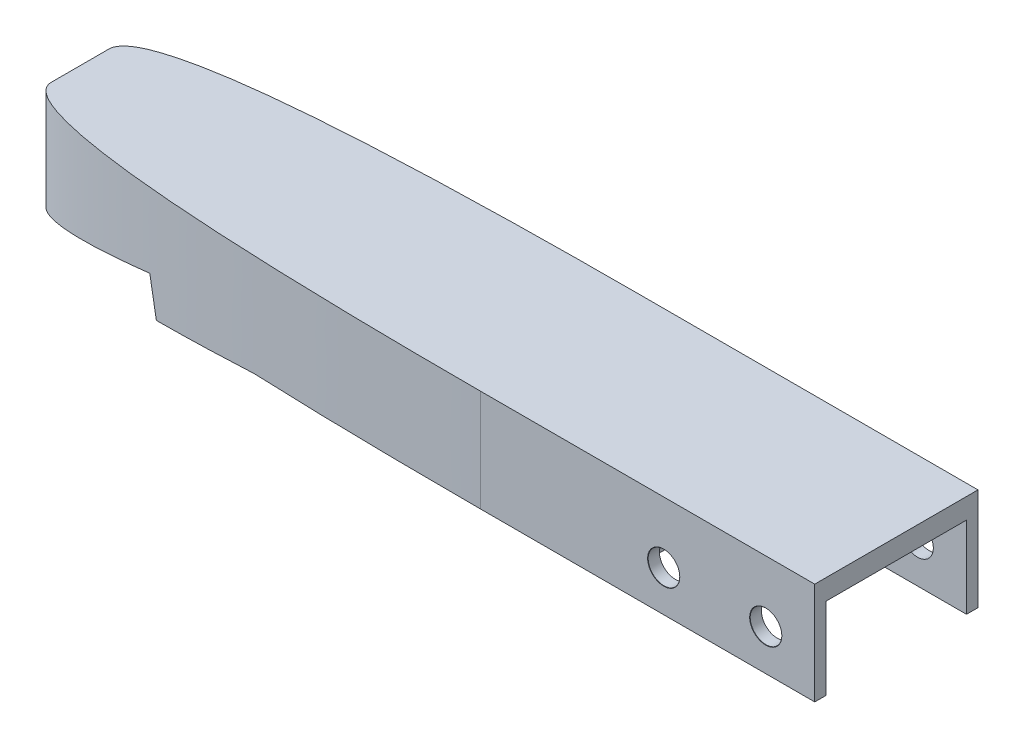
SolidWorks part; units mm, degrees
ref_plane "Front Plane" through (0, 0, 0) normal (0, 0, 1) x (1, 0, 0)
ref_plane "Top Plane" through (0, 0, 0) normal (0, 1, 0) x (1, 0, 0)
ref_plane "Right Plane" through (0, 0, 0) normal (1, 0, 0) x (0, 0, -1)
sketch "Sketch1" plane through (0, 0, 0) normal (0, 1, 0) x (1, 0, 0)
  line L1 (-40, 8) -> (40, 8)
  line L2 (-40, 8) -> (-40, -8)
  line L3 (-40, -8) -> (40, -8)
  line L4 (40, 8) -> (40, -8)
  line L5 (-40, 8) -> (40, -8) construction
  line L6 (-40, -8) -> (40, 8) construction
  point P0 (0, 0)
  dimension "D1" = 16
  dimension "D2" = 80
extrude "Boss-Extrude1" add sketch "Sketch1" along normal blind 10
sketch "Sketch3" plane through (0, 0, 0) normal (0, 1, 0) x (1, 0, 0)
  line L0 (40, -8) -> (40, 8) construction
  line L1 (40, -6.873) -> (19.746, -6.873)
  line L2 (40, -6.873) -> (40, 6.873)
  line L3 (40, 6.873) -> (19.746, 6.873)
  line L4 (19.746, -6.873) -> (19.746, 6.873)
  point P6 (19.746, 0)
  point P12 (40, 0)
  dimension "D1" = 13.746
  dimension "D2" = 20.254
extrude "Cut-Extrude1" cut sketch "Sketch3" along normal blind 8
sketch "Sketch4" plane through (0, 0, 8) normal (0, 0, 1) x (1, 0, 0)
  line L0 (25.2, 4) -> (35.2, 4) construction
  line L4 (19.746, 0) -> (40, 0)
  line L5 (19.746, 8) -> (19.746, 0)
  line L6 (40, 8) -> (19.746, 8)
  line L7 (40, 0) -> (40, 8)
  line L9 (19.746, 8) -> (19.746, 0) construction
  line L10 (40, 8) -> (19.746, 8) construction
  line L11 (40, 0) -> (40, 8) construction
  line L13 (19.746, 0) -> (40, 0)
  circle A0 centre (35.2, 4) radius 1.377
  circle A1 centre (25.2, 4) radius 1.377
  point P6 (30.2, 4)
  point P10 (19.746, 4)
  dimension "D2" = 2.754
  dimension "D3" = 10
  dimension "D4" = 4.8
  dimension "D1" = 0
sketch "Sketch6" plane through (0, 0, 8) normal (0, 0, 1) x (1, 0, 0)
  line L0 (-40, 10) -> (-40, 0) construction
  line L1 (-40, 0) -> (-26.2624, 2.6977)
  line L2 (-40, 0) -> (-40, -17.9177)
  line L3 (-40, -17.9177) -> (-22.2141, -17.9177)
  line L4 (-26.2624, 2.6977) -> (-22.2141, -17.9177)
  dimension "D1" = 101.11
  dimension "D2" = 14
  dimension "D3" = 90
extrude "Cut-Extrude3" cut sketch "Sketch6" against normal through all
sketch "Sketch9" plane through (0, 0, 8) normal (0, 0, 1) x (1, 0, 0)
  line L1 (-25.7326, 0) -> (-25.5531, -0.9142)
  line L7 (-25.5531, -0.9142) -> (-15.3096, 0)
  line L8 (-25.7326, 0) -> (40, 0) construction
  line L9 (-15.3096, 0) -> (-25.7326, 0)
  line L10 (-26.2624, 2.6977) -> (-25.7326, 0) construction
  dimension "D1" = 96.01
extrude "Boss-Extrude3" add sketch "Sketch9" against normal up to surface (16 mm away) up to face at (-8.6658, 3.783, -8)
sketch "Sketch7" plane through (0, 10, 0) normal (0, 1, 0) x (1, 0, 0)
  line L1 (40, 8) -> (-40, 8) construction
  line L2 (7.2698, 8) -> (-40, 8) construction
  line L3 (-40, 8) -> (-40, -8) construction
  line L4 (-40, 8) -> (-40, 2.8227) construction
  line L5 (7.2698, 8) -> (-40, 8)
  line L6 (-40, 8) -> (-40, 2.8227)
  spline S0 degree 2 poles (7.2698, 8) (-40, 8) (-40, 2.8227) knots 0 0 0 1 1 1
extrude "Cut-Extrude6" cut sketch "Sketch7" against normal through all
mirror "Mirror2" about plane through (0, 0, 0) normal (0, 0, 1) of "Cut-Extrude6"
hole_wizard "M2.5 Clearance Hole1" positions "Sketch10" profile "Sketch11" hole size "M2.5" standard "ANSI Metric" end condition through all
sketch "Sketch10" plane through (0, 0, 8) normal (0, 0, 1) x (1, 0, 0)
  point P0 (25.2, 4)
  point P3 (35.2, 4)
sketch "Sketch11" plane through (25.2, 4, 8) normal (1, 0, 0) x (0, -1, 0)
  line L0 (0, 0) -> (0, 16)
  line L1 (0, 16) -> (1.55, 16)
  line L2 (1.55, 16) -> (1.55, 0.025)
  line L3 (1.55, 0.025) -> (1.575, 0)
  line L5 (1.575, 0) -> (0, 0)
  line L6 (-1.55, 0.025) -> (-1.575, 0) construction
  line L11 (0, -6.35) -> (0, 107.95) construction
  dimension "Thru Hole Dia." = 3.1
  dimension "Thru Hole Depth" = 16
  dimension "Near C'Sink Dia." = 3.15
  dimension "Near C'Sink Angle" = 90
